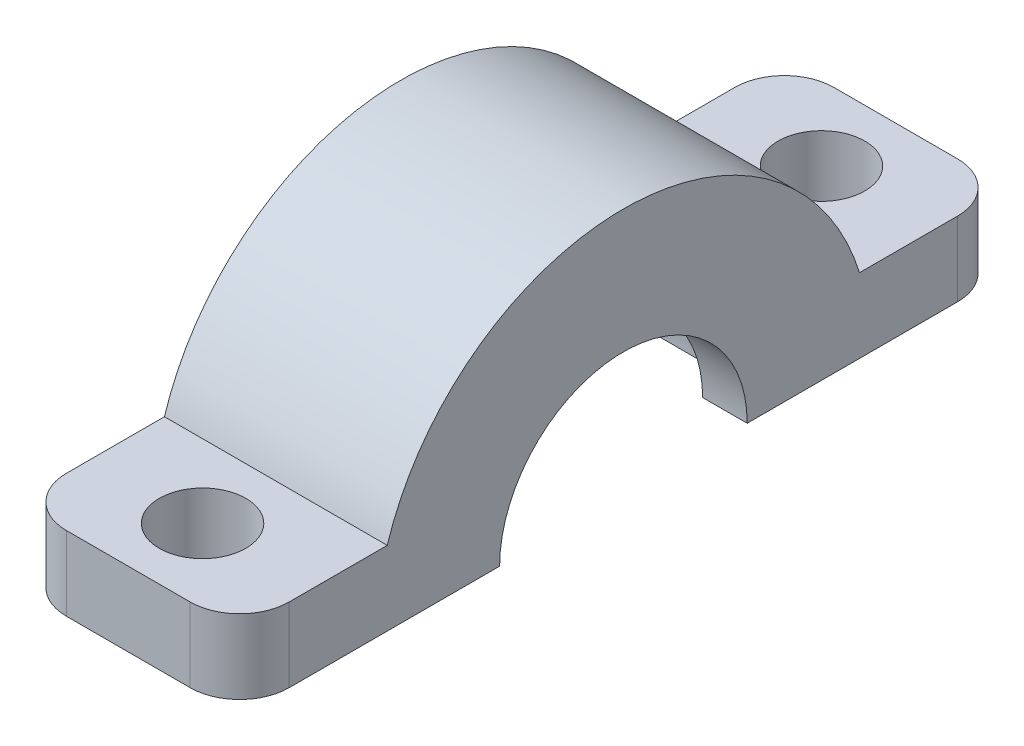
SolidWorks part; units mm, degrees
ref_plane "Front Plane" through (0, 0, 0) normal (0, 0, 1) x (1, 0, 0)
ref_plane "Top Plane" through (0, 0, 0) normal (0, 1, 0) x (1, 0, 0)
ref_plane "Right Plane" through (0, 0, 0) normal (1, 0, 0) x (0, 0, -1)
sketch "Sketch2" plane through (0, 0, 0) normal (1, 0, 0) x (0, 0, -1)
  line L0 (9.5394, 1.5) -> (15.5, 1.5)
  line L1 (-15.5, 1.5) -> (-9.5394, 1.5)
  line L2 (-15.5, 1.5) -> (-15.5, -1.5)
  line L3 (-15.5, -1.5) -> (-5, -1.5)
  line L4 (15.5, 1.5) -> (15.5, -1.5)
  line L5 (-4.6059, 0.4457) -> (15.5, -1.5) construction
  line L6 (-15.5, -1.5) -> (15.5, 1.5) construction
  line L7 (5, -1.5) -> (15.5, -1.5)
  arc A0 (9.5394, 1.5) -> (-9.5394, 1.5) centre (0, -1.5) ccw
  arc A1 (5, -1.5) -> (-5, -1.5) centre (0, -1.5) ccw
  point P0 (0, 0)
  dimension "D3" = 10
  dimension "D4" = 5
  dimension "D1" = 31
  dimension "D2" = 3
extrude "Boss-Extrude1" add sketch "Sketch2" along normal blind 4.5 and the other way blind 4.5
sketch "Sketch3" plane through (0, 1.5, 0) normal (0, 1, 0) x (1, 0, 0)
  line L0 (0, 12.5) -> (0, 0) construction
  line L1 (0, 0) -> (0, -12.5) construction
  line L2 (-4.5, -15.5) -> (4.5, -15.5) construction
  line L3 (-4.5, 15.5) -> (4.5, 15.5) construction
  circle A0 centre (0, 12.5) radius 1.75
  circle A1 centre (0, -12.5) radius 1.75
  dimension "D3" = 3.5
  dimension "D4" = 3.5
  dimension "D1" = 3
  dimension "D2" = 3
extrude "Cut-Extrude1" cut sketch "Sketch3" against normal through all
fillet "Fillet1" radius 2 4 edges at (4.5, 0, 15.5) (-4.5, 0, 15.5) (4.5, 0, -15.5) (-4.5, 0, -15.5)
sketch "Sketch4" plane through (0, 0, 0) normal (1, 0, 0) x (0, 0, -1)
  circle A0 centre (0, -1.5) radius 6.25
  dimension "D1" = 12.5
extrude "Cut-Extrude2" cut sketch "Sketch4" against normal blind 2.7 and the other way blind 2.7
